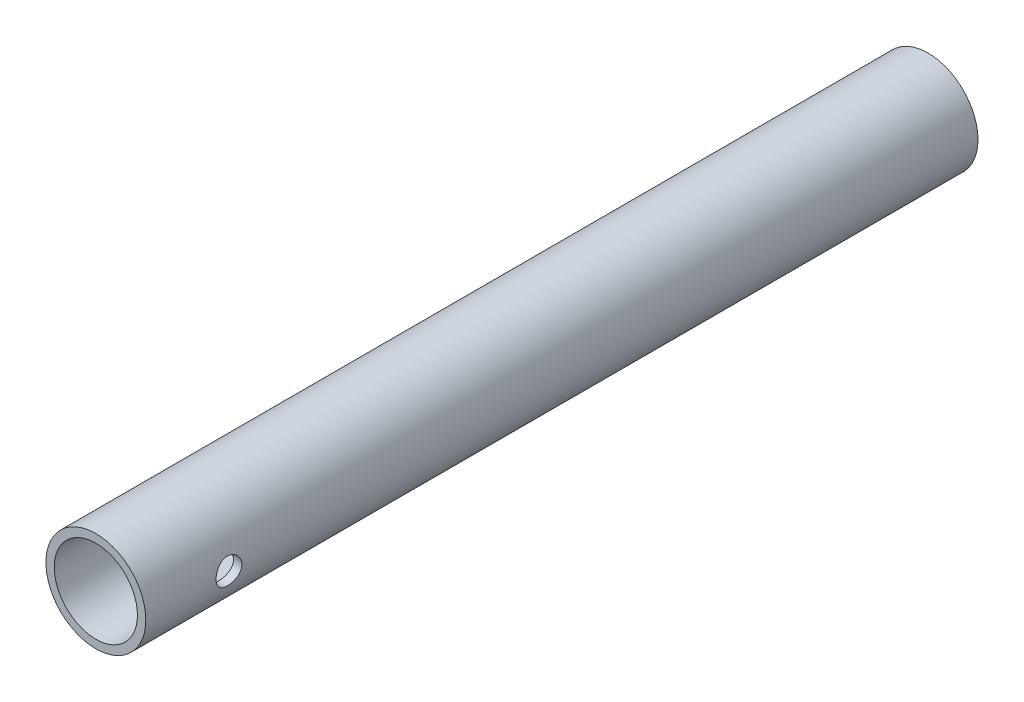
SolidWorks part; units mm, degrees
material "Thornel Mat VMA"
ref_plane "前视基准面" through (0, 0, 0) normal (0, 0, 1) x (1, 0, 0)
ref_plane "上视基准面" through (0, 0, 0) normal (0, 1, 0) x (1, 0, 0)
ref_plane "右视基准面" through (0, 0, 0) normal (1, 0, 0) x (0, 0, -1)
other "Configuration Table"
sketch "草图1" plane through (0, 0, 0) normal (0, 0, 1) x (1, 0, 0)
  circle A0 centre (0, 0) radius 5
  circle A1 centre (0, 0) radius 6
  dimension "D1" = 12
  dimension "D2" = 10
extrude "凸台-拉伸1" add sketch "草图1" along normal blind 100
sketch "草图2" plane through (0, 0, 0) normal (1, 0, 0) x (0, 0, -1)
  line L0 (0, 6) -> (-100, 6) construction
  line L1 (-100, 6) -> (-100, -6) construction
  circle A0 centre (-90, 0) radius 1.55
  dimension "D2" = 3.1
  dimension "D1" = 6
  dimension "D3" = 10
extrude "切除-拉伸1" cut sketch "草图2" against normal through all and the other way through all
